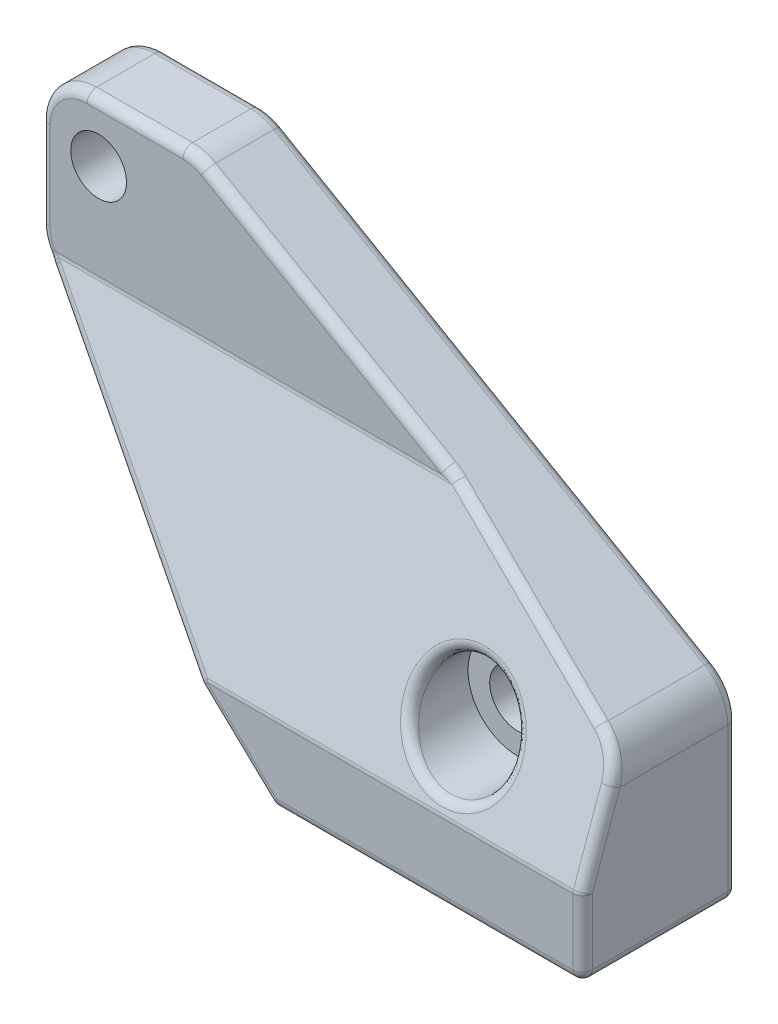
SolidWorks part; units mm, degrees
ref_plane "Front Plane" through (0, 0, 0) normal (0, 0, 1) x (1, 0, 0)
ref_plane "Top Plane" through (0, 0, 0) normal (0, 1, 0) x (1, 0, 0)
ref_plane "Right Plane" through (0, 0, 0) normal (1, 0, 0) x (0, 0, -1)
sketch "Sketch8" plane through (0, 0, 0) normal (0, 0, 1) x (1, 0, 0)
  line L0 (0, 0) -> (-25.4, 0)
  line L3 (-50.8, 36.83) -> (-38.1, 36.83)
  line L4 (-38.1, 36.83) -> (0, 14.833)
  line L5 (0, 14.833) -> (0, 0)
  line L6 (-50.8, 36.83) -> (-50.8, 24.13)
  line L7 (-50.8, 36.83) -> (-50.8, -7.62) construction
  line L8 (-50.8, 24.13) -> (-25.4, 0)
  circle A0 centre (-11.684, 11.43) radius 2.286 construction
  circle A1 centre (-46.0375, 32.0675) radius 2.286 construction
  circle A2 centre (-11.684, 11.43) radius 2.286
  circle A3 centre (-46.0375, 32.0675) radius 2.286
  dimension "D1" = 12.7
  dimension "D2" = 12.7
  dimension "D3" = 150
  dimension "D4" = 25.4
extrude "Boss-Extrude1" add sketch "Sketch8" along normal blind 12.7
sketch "Sketch9" plane through (0, 0, 0) normal (0, -1, 0) x (1, 0, 0)
  line L0 (0, 12.7) -> (0, 0) construction
  line L4 (-25.4, 12.7) -> (0, 12.7) construction
  circle A0 centre (-6.35, 6.35) radius 1.905
  circle A1 centre (-19.05, 6.35) radius 1.905
  dimension "D2" = 6.35
  dimension "D4" = 3.81
  dimension "D1" = 6.35
  dimension "D5" = 12.7
  dimension "D3" = 2
extrude "Cut-Extrude4" cut sketch "Sketch9" against normal blind 15.875
sketch "Sketch10" plane through (-50.8, 0, 0) normal (-1, 0, 0) x (0, 0, 1)
  line L0 (6.35, 36.83) -> (6.35, 24.13)
  line L1 (12.7, 36.83) -> (0, 36.83) construction
  line L2 (6.35, 24.13) -> (12.7, 6.35)
  line L3 (12.7, 24.13) -> (12.7, 0) construction
  line L4 (12.7, 6.35) -> (12.7, 36.83)
  line L5 (12.7, 36.83) -> (12.7, 24.13) construction
  line L6 (12.7, 36.83) -> (6.35, 36.83)
  line L7 (12.7, 0) -> (0, 0) construction
  dimension "D1" = 12.7
  dimension "D2" = 6.35
extrude "Cut-Extrude5" cut sketch "Sketch10" against normal through all
sketch "Sketch11" plane through (0, 0, 12.7) normal (0, 0, 1) x (1, 0, 0)
  circle A0 centre (-11.684, 11.43) radius 4.064
  dimension "D1" = 8.128
extrude "Cut-Extrude6" cut sketch "Sketch11" against normal offset from surface (6.35 mm away) 6.35 up to face at (-9.398, 11.43, 0)
fillet "Fillet1" radius 3.81 4 edges at (-50.8, 24.13, 3.175) (-50.8, 36.83, 3.175) (-38.1, 36.83, 3.175) (0, 14.833, 4.8352)
fillet "Fillet2" radius 0.7937 29 edges at (-9.004, 20.0314, 7.8138) (-0.5104, 14.5383, 9.7756) (-0.5104, 14.5383, 0) (-19.5604, 26.1262, 0) (-38.1348, 36.7002, 0) (-43.0554, 36.83, 0) (-49.6841, 35.7141, 0) (-50.8, 29.3928, 0) (-50.491, 24.2627, 0) (-50.0745, 23.5291, 6.5646) (-26.6594, 30.2248, 6.35) (-38.1348, 36.7002, 6.35) (-43.0554, 36.83, 6.35) (-49.6841, 35.7141, 6.35) (-50.7066, 24.9273, 6.35) (0, 0, 6.35) (0, 3.175, 12.7) (0, 9.4916, 11.578) (0, 6.3166, 0) (-28.7421, 3.175, 12.7) (-25.4, 0, 6.35) (-37.5071, 11.5017, 0) (-40.8492, 14.6767, 9.7262) (-12.7, 0, 12.7) (-12.7, 0, 0) (-16.0421, 6.35, 12.7) (-33.267, 24.13, 6.35) (-50.8, 29.3928, 6.35) (-11.684, 7.366, 12.3371)
